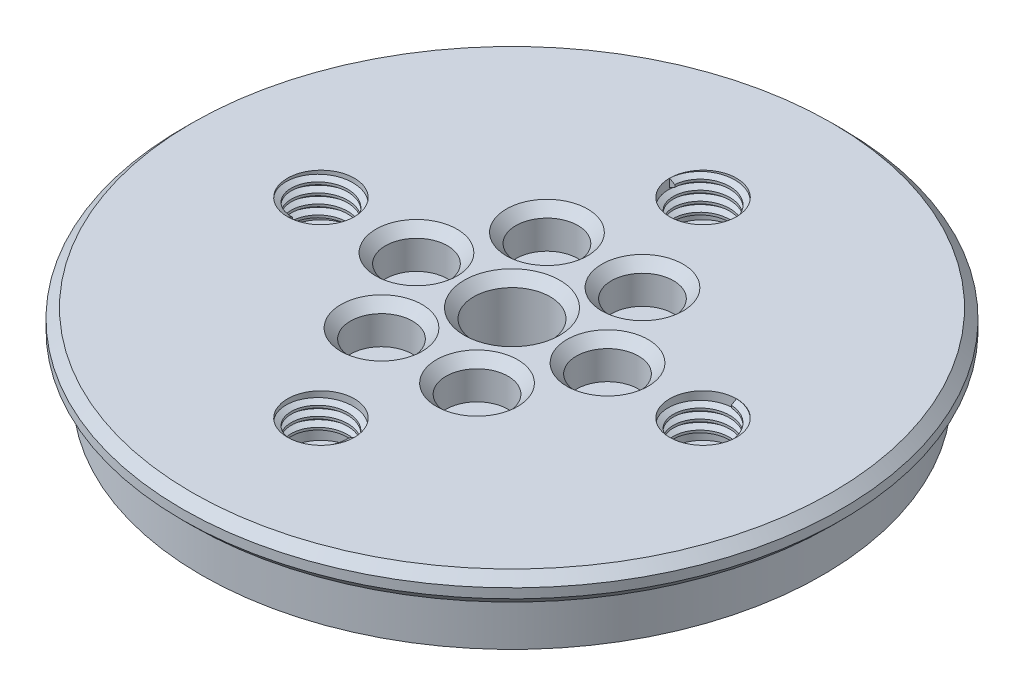
SolidWorks part; units mm, degrees
ref_plane "Front Plane" through (0, 0, 0) normal (0, 0, 1) x (1, 0, 0)
ref_plane "Top Plane" through (0, 0, 0) normal (0, 1, 0) x (1, 0, 0)
ref_plane "Right Plane" through (0, 0, 0) normal (1, 0, 0) x (0, 0, -1)
sketch "Sketch1" plane through (0, 0, 0) normal (0, 1, 0) x (1, 0, 0)
  circle A0 centre (0, 0) radius 32.5
  dimension "D1" = 65
extrude "Boss-Extrude1" add sketch "Sketch1" along normal blind 5
sketch "Sketch2" plane through (0, 0, 0) normal (0, 1, 0) x (1, 0, 0)
  circle A0 centre (0, 0) radius 13.5 construction
  circle A1 centre (-5, 8.6603) radius 1.25
  circle A2 centre (5, 8.6603) radius 1.25
  circle A3 centre (10, 0) radius 1.25
  circle A4 centre (5, -8.6603) radius 1.25
  circle A5 centre (-5, -8.6603) radius 1.25
  circle A6 centre (-10, 0) radius 1.25
  circle A7 centre (0, 0) radius 10 construction
  circle A8 centre (0, 0) radius 4
  point P3 (-10, 0)
  point P4 (-5, 8.6603)
  point P5 (5, 8.6603)
  point P6 (10, 0)
  point P7 (5, -8.6603)
  point P8 (-5, -8.6603)
  point P23 (0, 0)
  dimension "D1" = 27
  dimension "D2" = 2.5
  dimension "D4" = 20
  dimension "D5" = 8
  dimension "D3" = 6
sketch "Sketch3" plane through (0, 5, 0) normal (0, 1, 0) x (1, 0, 0)
  circle A0 centre (0, 0) radius 34.5
  dimension "D1" = 69
extrude "Boss-Extrude3" add sketch "Sketch3" along normal blind 3
extrude "Cut-Extrude1" cut sketch "Sketch2" along normal blind 11.5
sketch "Sketch4" plane through (0, 8, 0) normal (0, 1, 0) x (1, 0, 0)
  circle A1 centre (10, 0) radius 3.25
  circle A2 centre (5, 8.6603) radius 3.25
  circle A3 centre (5, 8.6603) radius 3.25
  circle A4 centre (5, -8.6603) radius 3.25
  circle A5 centre (-5, -8.6603) radius 3.25
  circle A6 centre (-10, 0) radius 3.25
  circle A7 centre (-5, 8.6603) radius 3.25
  point P15 (0, 0)
  dimension "D1" = 2
  dimension "D2" = 6
extrude "Cut-Extrude2" cut sketch "Sketch4" against normal offset from surface (4 mm away) 4 up to face at (5, 0, 9.9103)
sketch "Sketch5" plane through (0, 8, 0) normal (0, 1, 0) x (1, 0, 0)
  line L0 (0, 0) -> (0, 20) construction
  circle A0 centre (0, 0) radius 20 construction
  circle A1 centre (0, 20) radius 3.5
  circle A2 centre (20, 0) radius 3.5
  circle A3 centre (0, -20) radius 3.5
  circle A4 centre (-20, 0) radius 3.5
  point P14 (0, 0)
  dimension "D1" = 40
  dimension "D2" = 7
  dimension "D3" = 4
extrude "Cut-Extrude3" cut sketch "Sketch5" against normal offset from surface (4.5 mm away) 3.5 up to face at (5, 0, 9.9103)
thread "Thread1" pitch 1 method extrude profile "Thread Profile3" start angle 0, offset 0, length 3.5, pitch 1, diameter 7
ref_plane "Plane3" through (-3.5, 8, -20) normal (0, 0, 1) x (-1, 0, 0)
sketch "Thread Profile3" plane through (-3.5, 8, -20) normal (0, 0, 1) x (-1, 0, 0)
  line L0 (0, 0) -> (0, 1) construction
  line L11 (0, 0) -> (0, 0.875)
  line L12 (0, 0.875) -> (-0.5413, 0.5625)
  line L13 (-0.5413, 0.5625) -> (-0.5413, 0.3125)
  line L15 (-0.5413, 0.3125) -> (0, 0)
  line L17 (-0.5413, 0.4375) -> (0, 0.4375) construction
  point P2 (0, 0)
  dimension "Pitch" = 1
  dimension "Profile_Angle" = 60
  dimension "Profile_Land" = 0.25
  dimension "Profile_Height" = 0.5413
pattern_circular "CirPattern1" count 4 over 360 about axis through (0, 8, 0) along (0, -1, 0) of "Thread1"
chamfer "Chamfer1" distance 1 angle 45 10 edges at (0, 0, 4) (0, 8, 4) (0, 5, 34.5) (0, 8, 34.5) (5, 8, 11.9103) (-5, 8, 11.9103) (10, 8, 3.25) (5, 8, -5.4103) (-10, 8, 3.25) (-5, 8, -5.4103)
